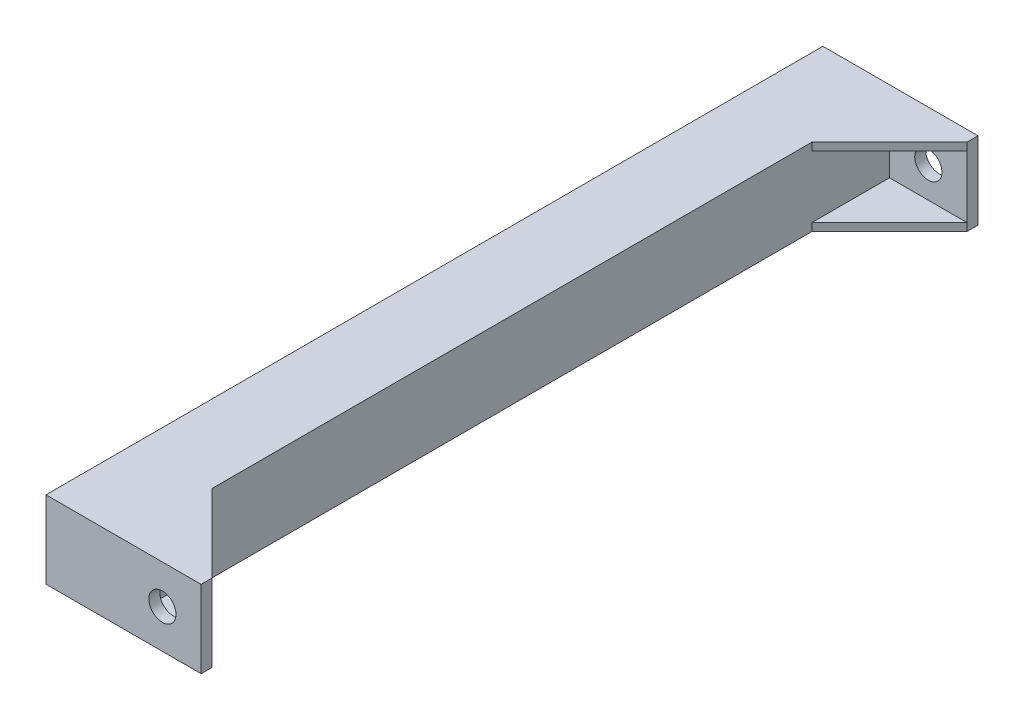
SolidWorks part; units mm, degrees
ref_plane "前视基准面" through (0, 0, 0) normal (0, 0, 1) x (1, 0, 0)
ref_plane "上视基准面" through (0, 0, 0) normal (0, 1, 0) x (1, 0, 0)
ref_plane "右视基准面" through (0, 0, 0) normal (1, 0, 0) x (0, 0, -1)
sketch "草图1" plane through (0, 0, 0) normal (0, 0, 1) x (1, 0, 0)
  line L5 (-14.9822, 4.9822) -> (4.9822, 4.9822)
  line L11 (-14.9822, 4.9822) -> (-14.9822, -4.9822)
  line L15 (-14.9822, -4.9822) -> (4.9822, -4.9822)
  line L16 (4.9822, 4.9822) -> (4.9822, -4.9822)
  line L17 (-14.9822, 4.9822) -> (4.9822, -4.9822) construction
  line L18 (-14.9822, -4.9822) -> (4.9822, 4.9822) construction
  circle A2 centre (0, 0) radius 1.75
extrude "凸台-拉伸1" add sketch "草图1" along normal blind 100
ref_plane "基准面2" through (0, 4.9822, 0) normal (0, 1, 0) x (1, 0, 0)
sketch "草图3" plane through (0, 4.9822, 0) normal (0, 1, 0) x (1, 0, 0)
  line L0 (-1.75, -100) -> (1.75, -100) construction
  line L1 (-1.75, -100) -> (1.75, -100)
  line L2 (-14.9822, -100) -> (-5, -100) construction
  line L3 (4.9822, -100) -> (-14.9822, -100) construction
  line L4 (-5, -100) -> (-5, 0) construction
  line L5 (4.9822, 0) -> (-14.9822, 0) construction
  line L6 (-5, 0) -> (4.9822, 0) construction
  line L7 (4.9822, -100) -> (4.9822, 0) construction
  line L10 (-5, -100) -> (4.9822, -100) construction
  line L12 (-5, -11.3941) -> (-5, -88.6057)
  line L18 (4.9822, -1.4141) -> (4.9822, -98.5862)
  line L19 (-4, -89.6057) -> (3.9822, -97.5862)
  line L21 (3.9822, -2.4138) -> (-4, -10.3943)
  line L23 (3.9822, -97.5862) -> (4.9822, -98.5862)
  line L24 (-4, -89.6057) -> (-5, -88.6057)
  line L25 (-4, -10.3943) -> (-5, -11.3941)
  line L26 (3.9822, -2.4138) -> (3.9822, -97.5862) construction
  line L27 (-4, -10.3943) -> (-4, -89.6057) construction
  line L28 (3.9822, -2.4138) -> (4.9822, -1.4141)
  line L30 (-5, -90.02) -> (4.9822, -100) construction
  line L31 (-5, -9.98) -> (-5, -90.02) construction
  line L32 (4.9822, 0) -> (4.9822, -100) construction
  line L33 (4.9822, 0) -> (-5, -9.98) construction
extrude "切除-拉伸2" cut sketch "草图3" against normal blind 10 contours L18 L12 region at (0.1815, 4.9822, 50)
ref_plane "基准面3" through (4.9822, 0, 0) normal (1, 0, 0) x (0, 0, -1)
sketch "草图6" plane through (4.9822, 0, 0) normal (1, 0, 0) x (0, 0, -1)
  line L0 (-49.9999, -8.3463) -> (-49.9999, 11.9617) construction
  line L2 (-11.3941, -4.9822) -> (-11.3941, 4.9822) construction
  line L3 (-11.3941, 3.9822) -> (-1.4141, 3.9822)
  line L4 (-1.4141, -4.9822) -> (-1.4141, 4.9822) construction
  line L5 (-88.6057, -3.9822) -> (-88.6057, 3.9822)
  line L6 (-11.3941, -3.9822) -> (-1.4141, -3.9822)
  line L7 (-1.4141, -3.9822) -> (-1.4141, 3.9822)
  line L8 (-11.3941, -3.9822) -> (-11.3941, 3.9822)
  line L9 (-98.5857, -3.9822) -> (-98.5857, 3.9822)
  line L10 (-88.6057, -3.9822) -> (-98.5857, -3.9822)
  line L11 (-88.6057, 3.9822) -> (-98.5857, 3.9822)
extrude "切除-拉伸3" cut sketch "草图6" against normal up to surface (9.9822 mm away) up to face at (-5, 0, 49.9999)
